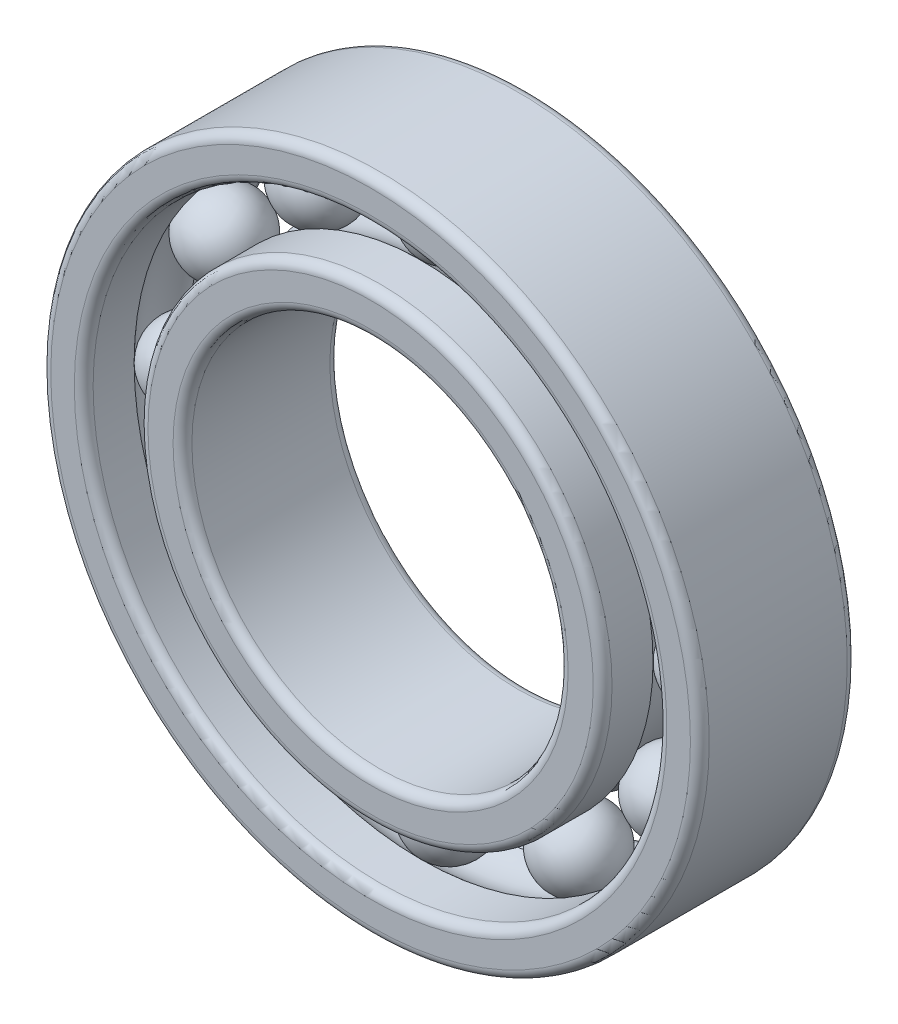
SolidWorks part; units mm, degrees
material "Legierter Stahl"
ref_plane "Ebene vorne" through (0, 0, 0) normal (0, 0, 1) x (1, 0, 0)
ref_plane "Ebene oben" through (0, 0, 0) normal (0, 1, 0) x (1, 0, 0)
ref_plane "Ebene rechts" through (0, 0, 0) normal (1, 0, 0) x (0, 0, -1)
sketch "Skizze1" plane through (0, 0, 0) normal (1, 0, 0) x (0, 0, -1)
  line L0 (0, 0) -> (32.8284, 0) construction
  line L1 (0, 0) -> (0, 22.1569) construction
  line L2 (-2.5, 10.5) -> (2.5, 10.5)
  line L3 (2.5, 10.5) -> (2.5, 9.15)
  line L4 (2.5, 9.15) -> (0.8927, 9.15)
  line L5 (0.8927, 7.4) -> (2.5, 7.4)
  line L6 (2.5, 7.4) -> (2.5, 6)
  line L7 (2.5, 6) -> (-2.5, 6)
  line L8 (-2.5, 7.4) -> (-2.5, 6)
  line L9 (-0.8927, 7.4) -> (-2.5, 7.4)
  line L10 (-2.5, 9.15) -> (-0.8927, 9.15)
  line L11 (-2.5, 10.5) -> (-2.5, 9.15)
  line L12 (-0.8927, 9.15) -> (0, 8.275) construction
  line L13 (0, 8.275) -> (0.8927, 7.4) construction
  line L14 (-1.25, 8.275) -> (1.25, 8.275)
  circle A0 centre (0, 8.275) radius 1.25
  point P17 (0, 6)
  point P22 (0, 10.5)
  dimension "D1" = 12
  dimension "D6" = 2.5
  dimension "D2" = 21
  dimension "D3" = 5
  dimension "D4" = 14.8
  dimension "D5" = 18.3
revolve "Rotation1" add sketch "Skizze1" angle 360 about L0 region at (0, 9.8634, 0) region at (0, 6.6613, 0)
revolve "Rotation3" add sketch "Skizze1<5>" angle 360 about L14 region at (0, 8.8055, 0)
sketch "Skizze1<5>" plane through (0, 0, 0) normal (1, 0, 0) x (0, 0, -1) same geometry as "Skizze1"
ref_axis "Achse1" through (0, 0, -2.5) along (0, 0, 1)
pattern_circular "Kreismuster4" count 12 over 360 about axis through (0, 0, -2.5) along (0, 0, 1) of bodies 110
fillet "Verrundung1" radius 0.3 4 edges at (9.15, 0, -2.5) (9.15, 0, 2.5) (10.5, 0, -2.5) (10.5, 0, 2.5)
fillet "Verrundung2" radius 0.3 4 edges at (7.4, 0, -2.5) (6, 0, -2.5) (7.4, 0, 2.5) (6, 0, 2.5)
